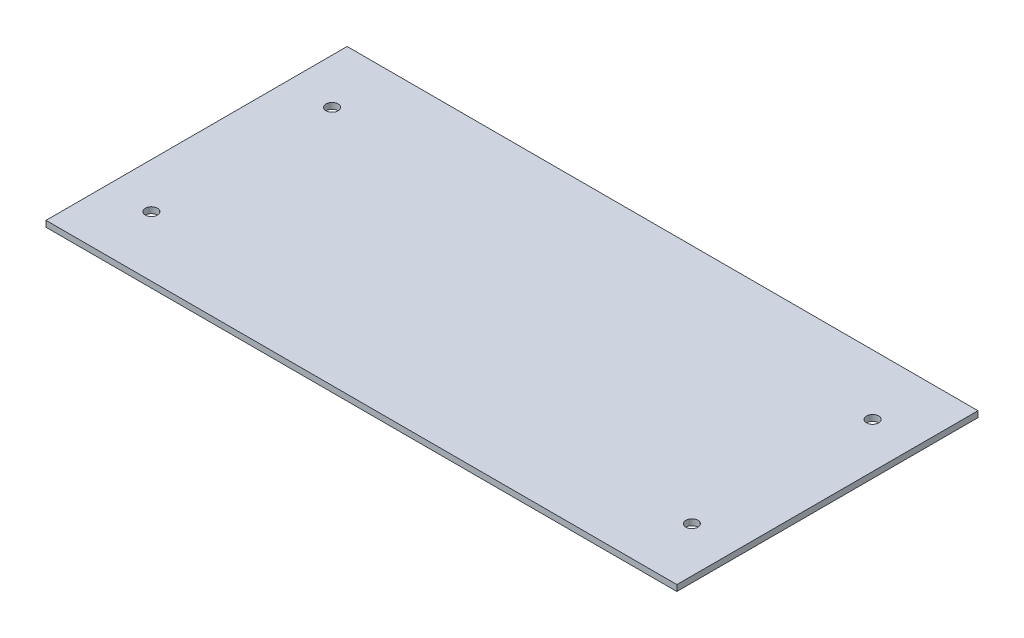
SolidWorks part; units mm, degrees
material "1060 Alloy"
ref_plane "Front Plane" through (0, 0, 0) normal (0, 0, 1) x (1, 0, 0)
ref_plane "Top Plane" through (0, 0, 0) normal (0, 1, 0) x (1, 0, 0)
ref_plane "Right Plane" through (0, 0, 0) normal (1, 0, 0) x (0, 0, -1)
sketch "Sketch1" plane through (0, 0, 0) normal (0, 1, 0) x (1, 0, 0)
  line L1 (-77.5877, 32.8522) -> (131.9123, 32.8522)
  line L2 (-77.5877, 32.8522) -> (-77.5877, -67.1478)
  line L3 (-77.5877, -67.1478) -> (131.9123, -67.1478)
  line L4 (131.9123, 32.8522) -> (131.9123, -67.1478)
  dimension "D1" = 209.5
  dimension "D2" = 100
extrude "Boss-Extrude1" add sketch "Sketch1" along normal blind 2
sketch "Sketch2" plane through (0, 2, 0) normal (0, 1, 0) x (1, 0, 0)
  line L0 (131.9123, 32.8522) -> (-77.5877, 32.8522) construction
  line L1 (131.9123, -67.1478) -> (131.9123, 32.8522) construction
  line L2 (-77.5877, 32.8522) -> (-77.5877, -67.1478) construction
  circle A0 centre (-62.5877, 12.8522) radius 2
  circle A1 centre (116.9123, 12.8522) radius 2
  circle A2 centre (-62.5877, -47.1478) radius 2
  circle A3 centre (116.9123, -47.1478) radius 2
  dimension "D1" = 179.5
  dimension "D2" = 4
  dimension "D3" = 4
  dimension "D5" = 15
  dimension "D6" = 20
  dimension "D7" = 4
  dimension "D8" = 4
  dimension "D9" = 60
  dimension "D10" = 60
  dimension "D11" = 15
  dimension "D12" = 15
  dimension "D4" = 20
extrude "Cut-Extrude1" cut sketch "Sketch2" against normal through all both and the other way through all
